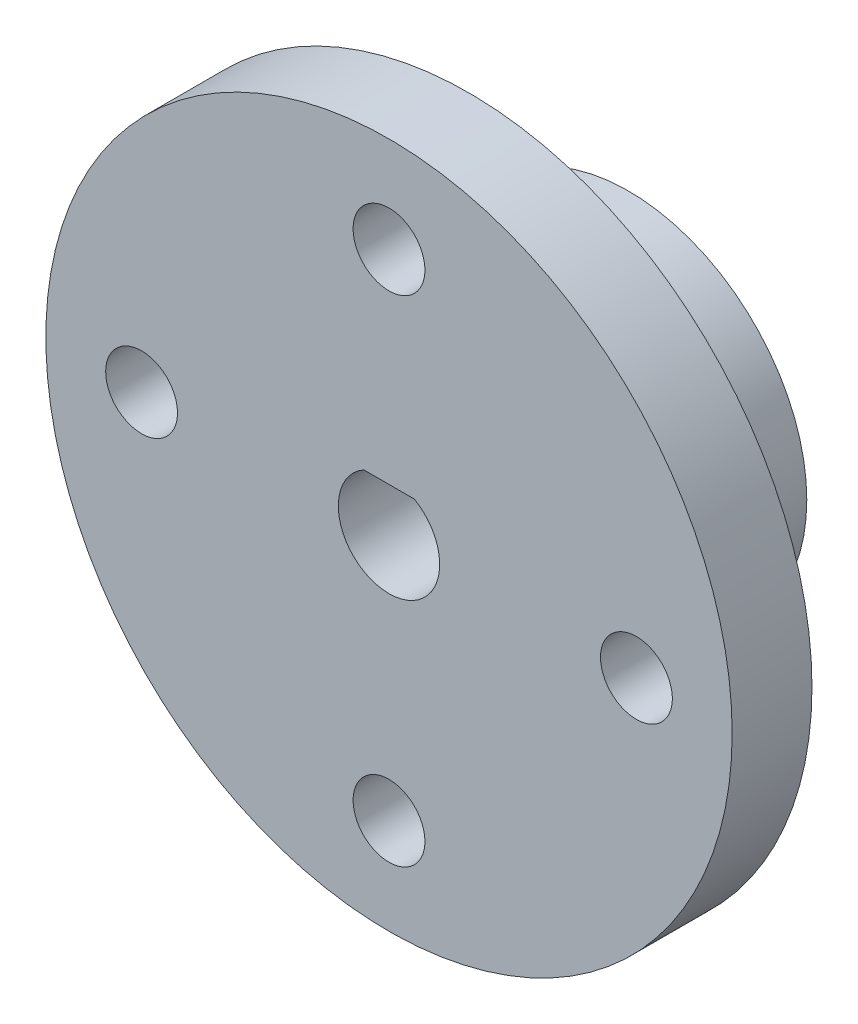
SolidWorks part; units mm, degrees
material "ABS"
ref_plane "Front Plane" through (0, 0, 0) normal (0, 0, 1) x (1, 0, 0)
ref_plane "Top Plane" through (0, 0, 0) normal (0, 1, 0) x (1, 0, 0)
ref_plane "Right Plane" through (0, 0, 0) normal (1, 0, 0) x (0, 0, -1)
sketch "Sketch1" plane through (0, 0, 0) normal (1, 0, 0) x (0, 0, -1)
  line L0 (-486.8485, 0) -> (23855.5787, 0) construction
  line L1 (0, 21.5) -> (5, 21.5)
  line L2 (5, 21.5) -> (9, 11.175)
  line L3 (9, 11.175) -> (15, 11.175)
  line L4 (15, 11.175) -> (15, 3.175)
  line L5 (15, 3.175) -> (0, 3.175)
  line L6 (0, 3.175) -> (0, 21.5)
  line L7 (0, 15.5) -> (7.3245, 15.5) construction
  dimension "D1" = 5
  dimension "D2" = 6.35
  dimension "D3" = 8
  dimension "D4" = 6
  dimension "D5" = 4
  dimension "D6" = 6
  dimension "D7" = 15.5
revolve "Revolve1" add sketch "Sketch1" angle 360 about L0
ref_plane "Plane1" through (0, 0, -9) normal (0, 0, 1) x (1, 0, 0)
sketch "Sketch3" plane through (0, 0, -9) normal (0, 0, 1) x (1, 0, 0)
  point P0 (0, 15.5)
hole_wizard "CBORE for M4 SHCS1" positions "Sketch3" profile "Sketch4" counterbore size "M4" standard "ANSI Metric" end condition through all
sketch "Sketch4" plane through (0, 15.5, -9) normal (1, 0, 0) x (0, 1, 0)
  line L0 (0, 0) -> (0, 9)
  line L1 (0, 9) -> (2.25, 9)
  line L3 (2.25, 9) -> (2.25, 4)
  line L4 (2.25, 4) -> (4, 4)
  line L5 (4, 4) -> (4, 0)
  line L7 (4, 0) -> (0, 0)
  line L11 (0, -6.35) -> (0, 107.95) construction
  dimension "Thru Hole Dia." = 4.5
  dimension "Thru Hole Depth" = 9
  dimension "C'Bore Dia." = 8
  dimension "C'Bore Depth" = 4
pattern_circular "CirPattern1" count 4 over 360 about axis through (0, 0, 486.8485) along (0, 0, 1) of "CBORE for M4 SHCS1" reverse direction yes
sketch "Sketch6" plane through (0, 0, 0) normal (0, 0, 1) x (1, 0, 0)
  line L0 (-1.5875, 2.7496) -> (1.5875, 2.7496)
  circle A0 centre (0, 0) radius 3.175 construction
  circle A1 centre (0, 0) radius 3.175
  dimension "D1" = 3.175
extrude "Boss-Extrude1" add sketch "Sketch6" against normal up to surface (15 mm away) contours L0 A1 region at (0, 2.9208, 0) up to face at (11.175, 0, -15)
sketch "Sketch8" plane through (0, 2.7496, 0) normal (0, -1, 0) x (1, 0, 0)
  line L0 (0, -15) -> (0, -12)
  line L1 (-11.175, -15) -> (11.175, -15) construction
  dimension "D1" = 3
sketch "Sketch9" plane through (0, 2.7496, 0) normal (0, -1, 0) x (-1, 0, 0)
  point P0 (0, 12)
hole_wizard "M3x0.5 Tapped Hole1" positions "Sketch9" profile "Sketch10" tap size "M3x0.5" standard "ANSI Metric" end condition through all
sketch "Sketch10" plane through (0, 2.7496, -12) normal (1, 0, 0) x (0, 0, -1)
  line L0 (0, 0) -> (0, 18.7504)
  line L1 (0, 18.7504) -> (1.25, 18.7504)
  line L2 (1.25, 18.7504) -> (1.25, 0)
  line L5 (1.25, 0) -> (0, 0)
  line L11 (0, -6.35) -> (0, 107.95) construction
  dimension "Thru Tap Drill Dia." = 2.5
  dimension "Thru Tap Drill Depth" = 18.7504
cosmetic thread "Hole Thread1" parameters "D2"=3
pattern_circular "CirPattern2" count 2 every 120 about axis through (0, 0, 486.8485) along (0, 0, 1) of "M3x0.5 Tapped Hole1"
cosmetic thread "Hole Thread2" parameters "D2"=3
chamfer "Chamfer1" distance 2 angle 45 1 edges at (11.175, 0, -9) first distance on face at (-9.0109, -6.6095, -12.2787)
